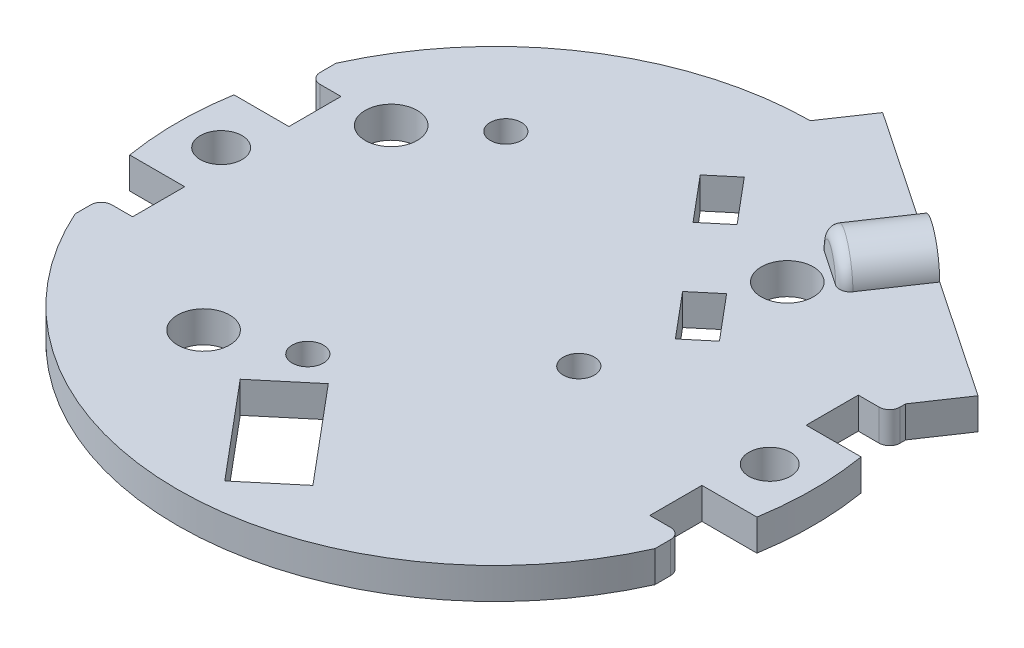
SolidWorks part; units mm, degrees
ref_plane "Alzado" through (0, 0, 0) normal (0, 0, 1) x (1, 0, 0)
ref_plane "Planta" through (0, 0, 0) normal (0, 1, 0) x (1, 0, 0)
ref_plane "Vista lateral" through (0, 0, 0) normal (1, 0, 0) x (0, 0, -1)
sketch "Croquis1" plane through (0, 0, 0) normal (0, 1, 0) x (1, 0, 0)
  circle A0 centre (0, 0) radius 30.5
extrude "Saliente-Extruir1" add sketch "Croquis1" along normal blind 3
sketch "Croquis5" plane through (0, 3, 0) normal (0, 1, 0) x (1, 0, 0)
  line L0 (0, 0) -> (0, 10)
  line L1 (28.8141, -5) -> (30.0874, -5)
  line L2 (28.8141, 5) -> (30.0874, 5)
  line L3 (-24.8141, 10) -> (-28.8141, 10)
  line L4 (24.8141, -5) -> (24.8141, -10)
  line L5 (-24.8141, -10) -> (-28.8141, -10)
  line L6 (24.8141, -5) -> (28.8141, -5)
  line L7 (24.8141, 5) -> (24.8141, 10)
  line L8 (-24.8141, 5) -> (-28.8141, 5)
  line L9 (-24.8141, 5) -> (-24.8141, 10)
  line L10 (-24.8141, -5) -> (-28.8141, -5)
  line L11 (-24.8141, -5) -> (-24.8141, -10)
  line L12 (24.8141, 5) -> (28.8141, 5)
  line L13 (24.8141, -10) -> (28.8141, -10)
  line L14 (24.8141, 10) -> (28.8141, 10)
  line L15 (-28.8141, 5) -> (-30.0874, 5)
  line L16 (-28.8141, -5) -> (-30.0874, -5)
  circle A1 centre (0, 0) radius 30.5 construction
  arc A2 (-28.8141, 10) -> (-30.0874, 5) centre (0, 0) ccw
  arc A3 (28.8141, 10) -> (28.8141, -10) centre (0, 0) cw
  arc A4 (-30.0874, -5) -> (-28.8141, -10) centre (0, 0) ccw
  arc A5 (30.0874, -5) -> (28.8141, -10) centre (0, 0) cw
  arc A6 (28.8141, 10) -> (30.0874, 5) centre (0, 0) cw
  circle M2 centre (0, 0) radius 30.5
extrude "Cortar-Extruir3" cut sketch "Croquis5" against normal blind 4 contours L11 L10 L8 L9 L3 L5 M2 | L15 L8 L9 L3 M2 | L14 L7 L12 L2 M2 | L4 L13 L1 L6 M2 region at (27.1844, 3, 7.3876) region at (27.1844, 3, -7.3876) region at (-27.1844, 3, 7.3876) region at (-27.1844, 3, -7.3876)
sketch "Croquis7" plane through (0, 3, 0) normal (0, 1, 0) x (1, 0, 0)
  line L0 (-8.1011, 29.1011) -> (9.5756, 8.0348)
  line L1 (9.5756, 8.0348) -> (27.2522, -13.0314)
  line L2 (-8.1011, 29.1011) -> (-27.2522, 13.0314)
  line L3 (27.2522, -13.0314) -> (8.1011, -29.1011)
  line L4 (8.1011, -29.1011) -> (-27.2522, 13.0314)
  line L5 (1.4284, 22.4114) -> (-0.8697, 20.4831)
  line L6 (1.4284, 22.4114) -> (4.6423, 18.5812)
  line L7 (4.6423, 18.5812) -> (2.3442, 16.6528)
  line L8 (2.3442, 16.6528) -> (-0.8697, 20.4831)
  line L9 (7.9686, 9.95) -> (11.1825, 6.1197)
  line L10 (8.1011, -29.1011) -> (5.53, -26.0369)
  line L11 (10.2667, 11.8783) -> (13.4807, 8.0481)
  line L12 (13.4807, 8.0481) -> (11.1825, 6.1197)
  line L13 (10.2667, 11.8783) -> (7.9686, 9.95)
  line L14 (5.53, -26.0369) -> (10.8923, -21.5374)
  line L15 (10.8923, -21.5374) -> (-19.3188, 14.4667)
  line L17 (-24.6811, 9.9672) -> (-19.3188, 14.4667)
  point P7 (-9.5756, -8.0348)
extrude "Cortar-Extruir5" cut sketch "Croquis7" against normal blind 4 contours L7 L6 L5 L0 | L11 L13 L0 L1 L12 region at (1.8863, 3, -19.5321) region at (10.7246, 3, -8.999)
sketch "Croquis8" plane through (0, 3, 0) normal (0, 1, 0) x (1, 0, 0)
  line L0 (-11.3137, 11.3137) -> (0, 0)
  line L2 (0, 0) -> (12, 0)
  line L3 (0, 0) -> (-11.3137, 11.3137)
  line L4 (12, 0) -> (12, 16)
  line L5 (0, 0) -> (-12, 0)
  line L6 (-12, 0) -> (-12, -16)
  line L10 (1.5586, -27.5246) -> (6.1549, -23.6679)
  line L11 (6.1549, -23.6679) -> (-1.5586, -14.4754)
  line L13 (-6.1549, -18.3321) -> (-1.5586, -14.4754)
  line L14 (1.5586, -27.5246) -> (-6.1549, -18.3321)
  circle A0 centre (0, 0) radius 30
  circle A1 centre (9, -1) radius 1.5
  circle A2 centre (-5, -13) radius 1.5
  circle A3 centre (-12, -16) radius 2.5
  circle A4 centre (-14, 15) radius 1.5
  circle A5 centre (12, 16) radius 2.5
  point P20 (-3.8567, -16.4037)
extrude "Cortar-Extruir6" cut sketch "Croquis8" against normal blind 10 contours L13 L10 L11 | A3 | L6 A3 | A3 L6 | A5 | L4 A5 | A5 L4 | L14 L10 L11 | L14 L11 | L13 L11 | A4 | L2 A1 | L2 A1 | A2 region at (10.2822, 3, -17.7178) region at (9, 3, -0.2032) region at (9, 3, 1.148) region at (-10.2822, 3, 14.2822) region at (0, 3, 21) region at (-5, 3, 13) region at (-14, 3, -15)
sketch "Croquis10" plane through (0, 3, 0) normal (0, 1, 0) x (1, 0, 0)
  line L0 (-24.8141, 10) -> (-27.8141, 10)
  line L2 (-24.8141, 10) -> (-28.8141, 10) construction
  line L4 (-27.8141, 10) -> (-27.8141, 12.5151)
  line L6 (-27.8141, 10) -> (-28.8141, 10)
  line L14 (-27.8141, -10) -> (-28.8141, -10)
  line L15 (-27.8141, -10) -> (-27.8141, -12.5151)
  line L16 (27.8141, -10) -> (27.8141, -12.5151)
  line L17 (27.8141, -10) -> (28.8141, -10)
  line L21 (27.8141, 10) -> (28.8141, 10)
  line L22 (27.8141, 10) -> (27.8141, 12.5151)
  line L23 (24.8141, 10) -> (27.8141, 10)
  circle A0 centre (-26.3141, 0) radius 2
  circle A1 centre (26.3141, 0) radius 2
  arc A2 (28.8141, 10) -> (-28.8141, 10) centre (0, 0) ccw construction
  arc A5 (-27.8141, 12.5151) -> (-28.8141, 10) centre (0, 0) ccw
  arc A7 (-27.8141, -12.5151) -> (-28.8141, -10) centre (0, 0) cw
  arc A8 (27.8141, -12.5151) -> (28.8141, -10) centre (0, 0) ccw
  arc A10 (27.8141, 12.5151) -> (28.8141, 10) centre (0, 0) cw
  line M13 (24.8141, 10) -> (28.8141, 10)
  arc M14 (28.8141, 10) -> (-28.8141, 10) centre (0, 0) ccw
  line M15 (-28.8141, 10) -> (-24.8141, 10)
  line M21 (-24.8141, -10) -> (-28.8141, -10)
  arc M22 (-28.8141, -10) -> (28.8141, -10) centre (0, 0) ccw
  line M23 (28.8141, -10) -> (24.8141, -10)
extrude "Cortar-Extruir8" cut sketch "Croquis10" against normal blind 3 contours L15 M21 M22 | L4 M15 M14 | L16 M23 M22 | L22 M13 M14 | A0 | A1 | L22 A10 L21 region at (-28.1547, 3, -10.8559) region at (28.1547, 3, -10.8559) region at (-28.1547, 3, 10.8559) region at (28.1547, 3, 10.8559) region at (-26.3141, 3, 0) region at (26.3141, 3, 0)
sketch "Croquis11" plane through (0, 3, 0) normal (0, 1, 0) x (1, 0, 0)
  line L0 (0, 0) -> (-20, 0)
  line L1 (-20, 0) -> (-20, 10)
  line L2 (0, 0) -> (0, 4.5949)
  line L3 (29.8013, 10.2046) -> (-1.7022, 31.454)
  circle A0 centre (-20, 10) radius 2.5
  circle A5 centre (0, 0) radius 31.5
  line M20 (27.8141, 10) -> (27.8141, 12.5151)
  arc M21 (27.8141, 12.5151) -> (-27.8141, 12.5151) centre (0, 0) ccw
extrude "Cortar-Extruir9" cut sketch "Croquis11" against normal blind 3 contours L3 M20 M21 | A0 region at (15.2326, 3, -22.6507) region at (-18.2822, 3, -8.2822)
sketch "Croquis13" plane through (14.0495, 0, -20.8293) normal (0.5592, 0, -0.829) x (-0.829, 0, -0.5592)
  line L1 (-16.603, 0) -> (17.2916, 0)
  line L2 (-16.603, 0) -> (-16.603, 3)
  line L3 (-16.603, 3) -> (17.2916, 3)
  line L4 (17.2916, 0) -> (17.2916, 3)
extrude "Saliente-Extruir2" add sketch "Croquis13" along normal blind 6
sketch "Croquis14" plane through (17.4047, 0, -25.8035) normal (0.5592, 0, -0.829) x (-0.829, 0, -0.5592)
  circle A0 centre (0.0043, 3) radius 3
extrude "Saliente-Extruir3" add sketch "Croquis14" against normal blind 8
sketch "Croquis17" plane through (17.4047, 0, -25.8035) normal (0.5592, 0, -0.829) x (-0.829, 0, -0.5592)
  circle A0 centre (0.0043, 3) radius 1.5
extrude "Cortar-Extruir10" cut sketch "Croquis17" against normal blind 7
sketch "Croquis19" plane through (17.4047, 0, -25.8035) normal (0.5592, 0, -0.829) x (-0.829, 0, -0.5592)
  line L0 (3.0043, 3) -> (17.2916, 3)
  line L1 (17.2916, 3) -> (17.2916, 0)
  line L2 (17.2916, 0) -> (-16.603, 0)
  line L3 (-16.603, 0) -> (-16.603, 3)
  line L4 (-16.603, 3) -> (-2.9957, 3)
  arc A0 (3.0043, 3) -> (-2.9957, 3) centre (0.0043, 3) ccw
extrude "Cortar-Extruir11" cut sketch "Croquis19" against normal blind 6
sketch "Croquis20" plane through (14.0495, 0, -20.8293) normal (0.5592, 0, -0.829) x (-0.829, 0, -0.5592)
  circle A0 centre (0.0043, 3) radius 1.5
  circle A1 centre (0.0043, 3) radius 3
extrude "Saliente-Extruir4" add sketch "Croquis20" along normal blind 5
fillet "Redondeo1" radius 1 1 edges at (12.9276, 6, -19.1736)
sketch "Croquis21" plane through (0, 3, 0) normal (0, 1, 0) x (1, 0, 0)
  line L0 (7.9686, 9.95) -> (10.2667, 11.8783)
  line L1 (7.9686, 9.95) -> (7.7758, 10.1798)
  line L2 (10.2667, 11.8783) -> (10.0739, 12.1081)
  line L3 (7.7758, 10.1798) -> (10.0739, 12.1081)
  line L4 (11.1825, 6.1197) -> (13.4807, 8.0481)
  line L5 (11.1825, 6.1197) -> (11.3754, 5.8899)
  line L6 (13.4807, 8.0481) -> (13.6735, 7.8183)
  line L7 (11.3754, 5.8899) -> (13.6735, 7.8183)
  line L8 (2.3442, 16.6528) -> (4.6423, 18.5812)
  line L9 (2.3442, 16.6528) -> (2.537, 16.423)
  line L10 (4.6423, 18.5812) -> (4.8352, 18.3514)
  line L11 (2.537, 16.423) -> (4.8352, 18.3514)
  line L12 (-0.8697, 20.4831) -> (1.4284, 22.4114)
  line L13 (-0.8697, 20.4831) -> (-1.0626, 20.7129)
  line L14 (1.4284, 22.4114) -> (1.2356, 22.6412)
  line L15 (-1.0626, 20.7129) -> (1.2356, 22.6412)
extrude "Cortar-Extruir12" cut sketch "Croquis21" against normal blind 3
fillet "Redondeo3" radius 1 4 edges at (-27.8141, 1.5, 10) (-27.8141, 1.5, -10) (27.8141, 1.5, 10) (27.8141, 1.5, -10)
sketch "Croquis22" plane through (14.0495, 0, -20.8293) normal (0.5592, 0, -0.829) x (-0.829, 0, -0.5592)
  line L0 (3.0043, 3) -> (17.2916, 3)
  line L1 (17.2916, 3) -> (17.2916, 0)
  line L2 (17.2916, 0) -> (-16.603, 0)
  line L3 (-16.603, 0) -> (-16.603, 3)
  line L4 (-16.603, 3) -> (-2.9957, 3)
  arc A0 (-2.9957, 3) -> (3.0043, 3) centre (0.0043, 3) ccw
  line M1 (17.2916, 3) -> (3.0043, 3)
  arc M2 (3.0043, 3) -> (0.0043, 0) centre (0.0043, 3) cw
  line M3 (0.0043, 0) -> (17.2916, 0)
  line M4 (17.2916, 0) -> (17.2916, 3)
extrude "Saliente-Extruir5" add sketch "Croquis22" along normal up to surface (5 mm away) contours A0 L4 L3 L2 | M4 M1 M2 M3 region at (21.8937, 1.4625, -15.5384) region at (5.9158, 1.4642, -26.3156) up to face at (14.3548, 3, -26.6545)
